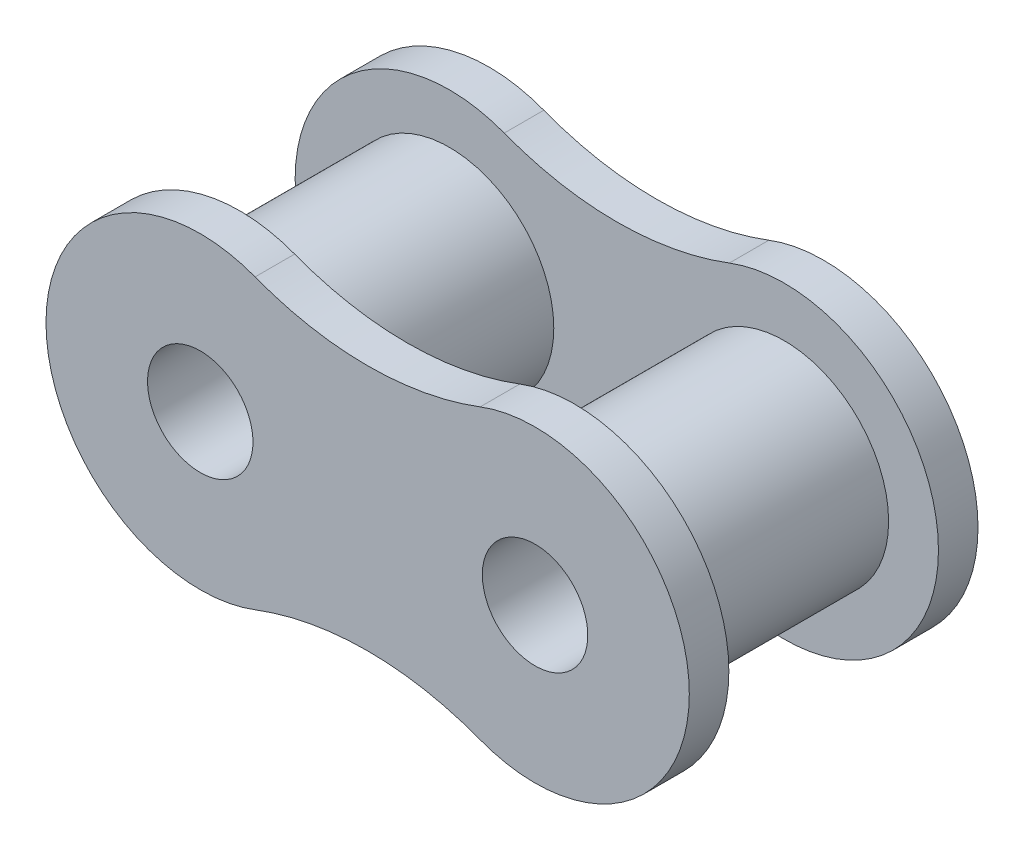
SolidWorks part; units mm, degrees
ref_plane "Front Plane" through (0, 0, 0) normal (0, 0, 1) x (1, 0, 0)
ref_plane "Top Plane" through (0, 0, 0) normal (0, 1, 0) x (1, 0, 0)
ref_plane "Right Plane" through (0, 0, 0) normal (1, 0, 0) x (0, 0, -1)
sketch "Sketch1" plane through (0, 0, 0) normal (0, 0, 1) x (1, 0, 0)
  line L0 (0, 0) -> (12.7, 0) construction
  arc A0 (2.0811, 5.4673) -> (2.0811, -5.4673) centre (0, 0) ccw
  arc A1 (10.6189, -5.4673) -> (10.6189, 5.4673) centre (12.7, 0) ccw
  arc A2 (2.0811, 5.4673) -> (10.6189, 5.4673) centre (6.35, 16.6823) ccw
  arc A3 (2.0811, -5.4673) -> (10.6189, -5.4673) centre (6.35, -16.6823) cw
  dimension "D2" = 11.7
  dimension "D3" = 11.7
  dimension "D4" = 12
  dimension "D1" = 12.7
extrude "Boss-Extrude1" add sketch "Sketch1" along normal blind 1.5
ref_plane "Plane1" through (0, 0, 5.475) normal (0, 0, 1) x (1, 0, 0)
mirror "Mirror2" about plane through (0, 0, 5.475) normal (0, 0, 1) of bodies 101
sketch "Sketch2" plane through (0, 0, 1.5) normal (0, 0, 1) x (1, 0, 0)
  circle A0 centre (0, 0) radius 3.96
  circle A1 centre (12.7, 0) radius 3.96
  dimension "D1" = 7.92
  dimension "D2" = 7.92
extrude "Boss-Extrude2" add sketch "Sketch2" along normal up to surface (7.95 mm away) up to face at (6.35, 0, 9.45)
sketch "Sketch3" plane through (0, 0, 0) normal (0, 0, -1) x (-1, 0, 0)
  circle A0 centre (0, 0) radius 2
  circle A1 centre (-12.7, 0) radius 2
  dimension "D1" = 4
  dimension "D2" = 4
extrude "Cut-Extrude1" cut sketch "Sketch3" against normal through all
